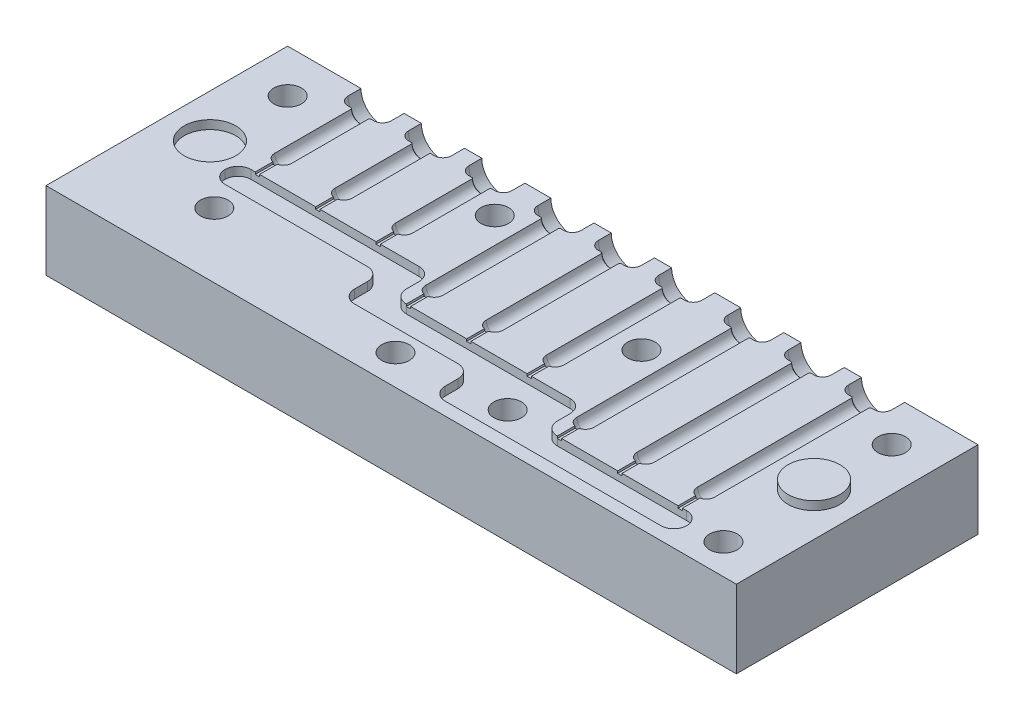
SolidWorks part; units mm, degrees
ref_plane "Ebene vorne" through (0, 0, 0) normal (0, 0, 1) x (1, 0, 0)
ref_plane "Ebene oben" through (0, 0, 0) normal (0, 1, 0) x (1, 0, 0)
ref_plane "Ebene rechts" through (0, 0, 0) normal (1, 0, 0) x (0, 0, -1)
sketch "Skizze1" plane through (0, 0, 0) normal (0, 1, 0) x (1, 0, 0)
  line L1 (0, 0) -> (80, 0)
  line L2 (0, 0) -> (0, 28)
  line L3 (0, 28) -> (80, 28)
  line L4 (80, 0) -> (80, 28)
  dimension "D1" = 80
  dimension "D2" = 28
extrude "Aufsatz-Linear austragen1" add sketch "Skizze1" along normal blind 9
sketch "Skizze2" plane through (0, 0, -28) normal (0, 0, -1) x (-1, 0, 0)
  line L0 (-80, 9) -> (0, 9) construction
  line L1 (-11, 9) -> (-18, 9) construction
  line L2 (-18, 9) -> (-25, 9) construction
  line L3 (-33, 9) -> (-40, 9) construction
  line L4 (-40, 9) -> (-47, 9) construction
  line L5 (-55, 9) -> (-62, 9) construction
  line L6 (-62, 9) -> (-69, 9) construction
  circle A0 centre (-11, 9) radius 1
  circle A1 centre (-18, 9) radius 1
  circle A2 centre (-25, 9) radius 1
  circle A3 centre (-33, 9) radius 1
  circle A4 centre (-40, 9) radius 1
  circle A5 centre (-47, 9) radius 1
  circle A6 centre (-55, 9) radius 1
  circle A7 centre (-62, 9) radius 1
  circle A8 centre (-69, 9) radius 1
  dimension "D1" = 2
  dimension "D2" = 7
  dimension "D3" = 11
  dimension "D5" = 8
  dimension "D4" = 3
extrude "Schnitt-Linear austragen1" cut sketch "Skizze2" against normal blind 12.5 contours A0 | A1 | A2
extrude "Schnitt-Linear austragen2" cut sketch "Skizze2<4>" against normal blind 17 contours A3 | A4 | A5
sketch "Skizze2<4>" plane through (0, 0, -28) normal (0, 0, -1) x (-1, 0, 0) same geometry as "Skizze2"
extrude "Schnitt-Linear austragen3" cut sketch "Skizze2<5>" against normal blind 21.5 contours A6 | A7 | A8
sketch "Skizze2<5>" plane through (0, 0, -28) normal (0, 0, -1) x (-1, 0, 0) same geometry as "Skizze2"
sketch "Skizze4" plane through (0, 0, -28) normal (0, 0, -1) x (-1, 0, 0)
  circle A0 centre (-11, 9) radius 2.5
  circle A1 centre (-18, 9) radius 2.5
  circle A2 centre (-25, 9) radius 2.5
  arc A3 (-12, 9) -> (-10, 9) centre (-11, 9) ccw construction
  arc A4 (-19, 9) -> (-17, 9) centre (-18, 9) ccw construction
  arc A5 (-26, 9) -> (-24, 9) centre (-25, 9) ccw construction
  circle A6 centre (-33, 9) radius 2.5
  circle A7 centre (-40, 9) radius 2.5
  circle A8 centre (-47, 9) radius 2.5
  circle A9 centre (-55, 9) radius 2.5
  circle A10 centre (-62, 9) radius 2.5
  circle A11 centre (-69, 9) radius 2.5
  dimension "D1" = 5
  dimension "D2" = 3
extrude "Schnitt-Linear austragen4" cut sketch "Skizze4" against normal blind 2.5
fillet "Verrundung1" radius 1 18 edges at (69, 6.5, -25.5) (62, 6.5, -25.5) (55, 6.5, -25.5) (47, 6.5, -25.5) (40, 6.5, -25.5) (33, 6.5, -25.5) (25, 6.5, -25.5) (18, 6.5, -25.5) (11, 6.5, -25.5) (11, 8, -15.5) (18, 8, -15.5) (25, 8, -15.5) (33, 8, -11) (40, 8, -11) (47, 8, -11) (55, 8, -6.5) (62, 8, -6.5) (69, 8, -6.5)
chamfer "Fase1" distance 0.1 angle 45 9 edges at (18, 8, -25.5) (11, 8, -25.5) (25, 8, -25.5) (47, 8, -25.5) (40, 8, -25.5) (33, 8, -25.5) (55, 8, -25.5) (62, 8, -25.5) (69, 8, -25.5)
sketch "Skizze5" plane through (0, 9, 0) normal (0, 1, 0) x (1, 0, 0)
  line L0 (11, 15.5) -> (11, 13.5) construction
  line L1 (33, 11) -> (33, 9) construction
  line L2 (10.75, 13.5) -> (11, 13.5)
  line L3 (10.75, 16.5) -> (10.75, 13.5)
  line L4 (11.25, 13.5) -> (11, 13.5)
  line L5 (32.75, 9) -> (33, 9)
  line L6 (32.75, 12) -> (32.75, 9)
  line L7 (33, 9) -> (33.25, 9)
  line L8 (10.75, 16.5) -> (11.25, 16.5)
  line L9 (55, 6.5) -> (55, 4.5) construction
  line L10 (17.75, 13.5) -> (18, 13.5)
  line L11 (33.25, 11) -> (33.25, 9) construction
  line L12 (32.75, 11) -> (32.75, 9) construction
  line L13 (32.75, 12) -> (33.25, 12)
  line L14 (54.75, 4.5) -> (55, 4.5)
  line L15 (54.75, 7.5) -> (54.75, 4.5)
  line L16 (55, 4.5) -> (55.25, 4.5)
  line L17 (54.75, 6.5) -> (54.75, 4.5) construction
  line L18 (11.25, 16.5) -> (11.25, 13.5)
  line L19 (33.25, 12) -> (33.25, 9)
  line L20 (17.75, 16.5) -> (17.75, 13.5)
  line L21 (18.25, 13.5) -> (18, 13.5)
  line L22 (55.25, 6.5) -> (55.25, 4.5) construction
  line L23 (54.75, 7.5) -> (55.25, 7.5)
  line L24 (55.25, 7.5) -> (55.25, 4.5)
  line L25 (39.75, 9) -> (40, 9)
  line L26 (39.75, 12) -> (39.75, 9)
  line L27 (11.25, 15.5) -> (11.25, 13.5) construction
  line L28 (10.75, 15.5) -> (10.75, 13.5) construction
  line L29 (17.75, 16.5) -> (18.25, 16.5)
  line L30 (18.25, 16.5) -> (18.25, 13.5)
  line L31 (18, 15.5) -> (18, 13.5) construction
  line L32 (24.75, 13.5) -> (25, 13.5)
  line L33 (24.75, 16.5) -> (24.75, 13.5)
  line L34 (25.25, 13.5) -> (25, 13.5)
  line L35 (24.75, 16.5) -> (25.25, 16.5)
  line L36 (25.25, 16.5) -> (25.25, 13.5)
  line L37 (25, 15.5) -> (25, 13.5) construction
  line L38 (40, 9) -> (40.25, 9)
  line L39 (39.75, 12) -> (40.25, 12)
  line L40 (40.25, 12) -> (40.25, 9)
  line L41 (40, 11) -> (40, 9) construction
  line L42 (46.75, 9) -> (47, 9)
  line L43 (46.75, 12) -> (46.75, 9)
  line L44 (47, 9) -> (47.25, 9)
  line L45 (46.75, 12) -> (47.25, 12)
  line L46 (47.25, 12) -> (47.25, 9)
  line L47 (47, 11) -> (47, 9) construction
  line L48 (61.75, 4.5) -> (62, 4.5)
  line L49 (61.75, 7.5) -> (61.75, 4.5)
  line L50 (62, 4.5) -> (62.25, 4.5)
  line L51 (61.75, 7.5) -> (62.25, 7.5)
  line L52 (62.25, 7.5) -> (62.25, 4.5)
  line L53 (62, 6.5) -> (62, 4.5) construction
  line L54 (68.75, 4.5) -> (69, 4.5)
  line L55 (68.75, 7.5) -> (68.75, 4.5)
  line L56 (69, 4.5) -> (69.25, 4.5)
  line L57 (68.75, 7.5) -> (69.25, 7.5)
  line L58 (69.25, 7.5) -> (69.25, 4.5)
  line L59 (69, 6.5) -> (69, 4.5) construction
  dimension "D1" = 2
  dimension "D2" = 0.5
  dimension "D4" = 7
  dimension "D5" = 3
  dimension "D6" = 7
  dimension "D8" = 7
  dimension "D3" = 3
  dimension "D7" = 3
extrude "Schnitt-Linear austragen5" cut sketch "Skizze5" against normal blind 0.25
sketch "Skizze6" plane through (0, 9, 0) normal (0, 1, 0) x (1, 0, 0)
  line L0 (31.25, 13.5) -> (8.75, 13.5)
  line L1 (31.25, 9) -> (53.25, 9)
  line L2 (31.25, 13.5) -> (31.25, 9)
  line L3 (25.25, 13.5) -> (25.25, 15.5318) construction
  line L4 (39.75, 9) -> (40.25, 9) construction
  line L5 (53.25, 9) -> (53.25, 4.5)
  line L6 (53.25, 4.5) -> (71.25, 4.5)
  line L7 (8.75, 13.5) -> (8.75, 10.5)
  line L8 (8.75, 10.5) -> (28.25, 10.5)
  line L9 (28.25, 10.5) -> (28.25, 6)
  line L10 (28.25, 6) -> (43.25, 6)
  line L11 (43.25, 6) -> (43.25, 1.5)
  line L12 (43.25, 1.5) -> (71.25, 1.5)
  line L13 (71.25, 1.5) -> (71.25, 4.5)
  line L14 (53.25, 4.5) -> (43.25, 4.5) construction
  line L15 (31.25, 9) -> (31.25, 6) construction
  line L16 (28.25, 10.5) -> (31.25, 10.5) construction
  line L17 (47.25, 9) -> (47.25, 11.0318) construction
  line L18 (68.75, 4.5) -> (69.25, 4.5) construction
  line L19 (10.75, 13.5) -> (11.25, 13.5) construction
  dimension "D1" = 6
  dimension "D2" = 3
  dimension "D3" = 6
  dimension "D4" = 10
  dimension "D5" = 2
  dimension "D6" = 2
extrude "Schnitt-Linear austragen6" cut sketch "Skizze6" against normal blind 1
sketch "Skizze7" plane through (0, 8, 0) normal (0, 1, 0) x (1, 0, 0)
  line L0 (43.25, 6) -> (53.25, 4.5) construction
  circle A0 centre (48.25, 5.25) radius 1.6
  dimension "D1" = 3.2
extrude "Schnitt-Linear austragen7" cut sketch "Skizze7" against normal up to next
hole_wizard "Durchgangsloch für M31" positions "Skizze9" profile "Skizze8" hole size "M3" standard "DIN" end condition through all
sketch "Skizze9" plane through (0, 9, 0) normal (0, 1, 0) x (1, 0, 0)
  line L0 (0, 28) -> (0, 0) construction
  line L1 (8.5, 28) -> (0, 28) construction
  line L2 (5, 23) -> (29, 23)
  line L5 (29, 23) -> (75, 23)
  line L7 (80, 0) -> (80, 28) construction
  line L8 (75, 3.5) -> (37, 3.5)
  line L9 (37, 3.5) -> (12, 3.5)
  line L10 (12, 3.5) -> (12, 7.5)
  line L12 (0, 0) -> (80, 0) construction
  point P0 (29, 23)
  point P2 (51, 18)
  point P4 (75, 23)
  point P6 (75, 3.5)
  point P8 (12, 7.5)
  point P10 (5, 23)
  point P34 (37, 3.5)
  dimension "D1" = 5
  dimension "D2" = 5
  dimension "D3" = 29
  dimension "D4" = 5
  dimension "D5" = 29
  dimension "D6" = 5
  dimension "D7" = 12
  dimension "D8" = 5
  dimension "D9" = 3.5
  dimension "D10" = 4
  dimension "D11" = 25
sketch "Skizze8" plane through (29, 9, -23) normal (1, 0, 0) x (0, 0, 1)
  line L0 (0, 0) -> (0, 9)
  line L1 (0, 9) -> (1.6, 9)
  line L2 (1.6, 9) -> (1.6, 0)
  line L5 (1.6, 0) -> (0, 0)
  line L11 (0, -6.35) -> (0, 107.95) construction
  dimension "Bohrerdurchmesser" = 3.2
  dimension "Bohrungstiefe" = 9
sketch "Skizze10" plane through (0, 9, 0) normal (0, 1, 0) x (1, 0, 0)
  line L0 (0, 14) -> (5, 14) construction
  line L1 (0, 28) -> (0, 0) construction
  line L2 (5, 14) -> (75, 14) construction
  line L3 (75, 14) -> (80, 14) construction
  line L4 (80, 0) -> (80, 28) construction
  circle A0 centre (5, 14) radius 3
  circle A1 centre (75, 14) radius 3
  dimension "D1" = 6
  dimension "D2" = 5
extrude "Schnitt-Linear austragen8" cut sketch "Skizze10" against normal blind 1 contours A0
extrude "Aufsatz-Linear austragen2" add sketch "Skizze10<3>" along normal blind 1 contours A1 region at (75, 9, -14)
sketch "Skizze10<3>" plane through (0, 9, 0) normal (0, 1, 0) x (1, 0, 0) same geometry as "Skizze10"
fillet "Verrundung2" radius 1.5 12 edges at (71.25, 8.5, -1.5) (71.25, 8.5, -4.5) (53.25, 8.5, -4.5) (53.25, 8.5, -9) (43.25, 8.5, -1.5) (43.25, 8.5, -6) (28.25, 8.5, -10.5) (31.25, 8.5, -13.5) (28.25, 8.5, -6) (31.25, 8.5, -9) (8.75, 8.5, -10.5) (8.75, 8.5, -13.5)
